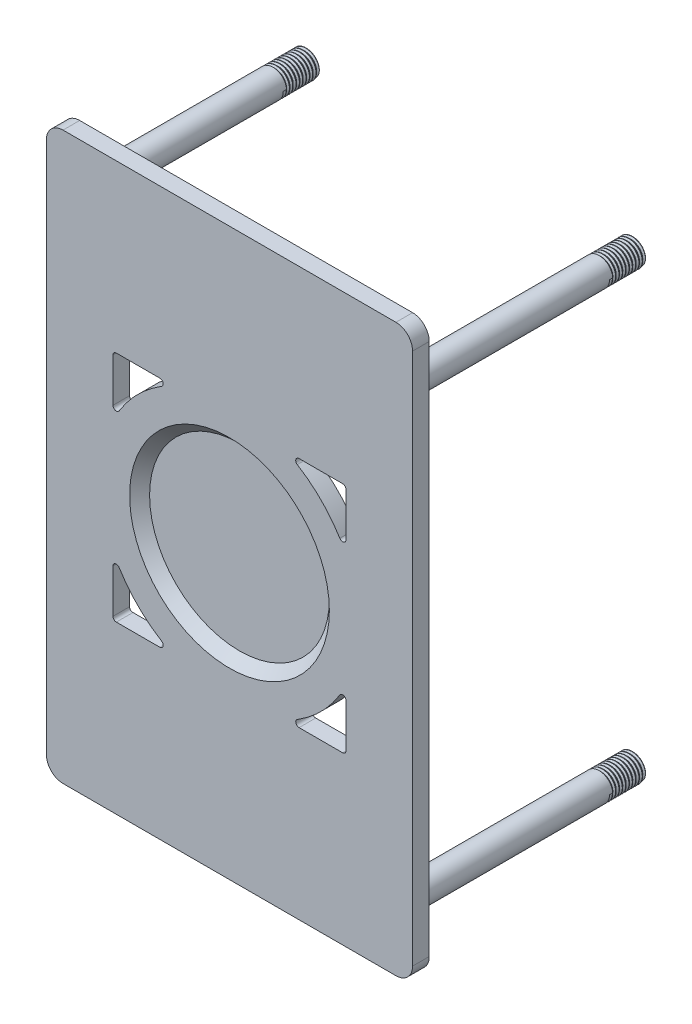
SolidWorks part; units mm, degrees
ref_plane "Ebene vorne" through (0, 0, 0) normal (0, 0, 1) x (1, 0, 0)
ref_plane "Ebene oben" through (0, 0, 0) normal (0, 1, 0) x (1, 0, 0)
ref_plane "Ebene rechts" through (0, 0, 0) normal (1, 0, 0) x (0, 0, -1)
sketch "Skizze1" plane through (0, 0, 0) normal (0, 0, 1) x (1, 0, 0)
  line L1 (-55, -85) -> (55, -85)
  line L2 (-55, -85) -> (-55, 85)
  line L3 (-55, 85) -> (55, 85)
  line L4 (55, -85) -> (55, 85)
  line L5 (-55, -85) -> (55, 85) construction
  line L6 (-55, 85) -> (55, -85) construction
  point P0 (0, 0)
  dimension "D1" = 110
  dimension "D2" = 170
extrude "Aufsatz-Linear austragen1" add sketch "Skizze1" along normal blind 5
sketch "Skizze2" plane through (0, 0, 5) normal (0, 0, 1) x (1, 0, 0)
  line L0 (-55, -85) -> (55, -85) construction
  line L1 (0, 85) -> (0, -85) construction
  line L2 (55, 85) -> (-55, 85) construction
  circle A1 centre (0, 0) radius 27
  dimension "D2" = 54
fillet "Verrundung1" radius 5 4 edges at (-55, -85, 2.5) (55, -85, 2.5) (55, 85, 2.5) (-55, 85, 2.5)
sketch "Skizze3" plane through (0, 0, 5) normal (0, 0, 1) x (1, 0, 0)
  line L0 (-35, 35) -> (-35, 17)
  line L1 (-35, -35) -> (35, -35) construction
  line L2 (-35, -35) -> (-35, 35) construction
  line L3 (-35, 35) -> (35, 35) construction
  line L4 (35, -35) -> (35, 35) construction
  line L5 (-35, -35) -> (35, 35) construction
  line L6 (-35, 35) -> (35, -35) construction
  line L7 (-35, 35) -> (-17, 35)
  line L8 (35, 35) -> (17, 35)
  line L9 (35, 35) -> (35, 17)
  line L10 (35, -35) -> (35, -17)
  line L11 (35, -35) -> (17, -35)
  line L12 (-35, -35) -> (-17, -35)
  line L13 (-35, -35) -> (-35, -17)
  arc A0 (-17, 35) -> (-35, 17) centre (0, 0) ccw
  arc A1 (35, 17) -> (17, 35) centre (0, 0) ccw
  arc A2 (17, -35) -> (35, -17) centre (0, 0) ccw
  arc A3 (-35, -17) -> (-17, -35) centre (0, 0) ccw
  point P0 (0, 0)
  point P21 (0, 0)
  dimension "D2" = 18
  dimension "D1" = 70
  dimension "D3" = 4
extrude "Schnitt-Linear austragen1" cut sketch "Skizze3" against normal through all
extrude "Schnitt-Linear austragen2" cut sketch "Skizze2" against normal blind 3
chamfer "Fase1" distance 3 angle 45 1 edges at (27, 0, 5)
sketch "Skizze4" plane through (0, 0, 0) normal (0, 0, -1) x (-1, 0, 0)
  line L0 (-50, 85) -> (50, 85) construction
  line L1 (-55, -80) -> (-55, 80) construction
  circle A0 centre (-49, 67) radius 4
  dimension "D1" = 18
  dimension "D3" = 8
  dimension "D2" = 6
extrude "Aufsatz-Linear austragen2" add sketch "Skizze4" along normal blind 69
chamfer "Fase2" distance 1 angle 45 1 edges at (45, 67, 0)
ref_plane "Ebene1" through (0, 0, -67) normal (0, 0, -1) x (-1, 0, 0)
sketch "Skizze5" plane through (0, 0, -67) normal (0, 0, -1) x (-1, 0, 0)
  circle A0 centre (-49, 67) radius 3
  circle A1 centre (-49, 67) radius 3.5
  dimension "D1" = 6
  dimension "D2" = 7
extrude "Schnitt-Linear austragen3" [suppressed] cut sketch "Skizze5" against normal blind 1
pattern_linear "Lineares Muster1" count 2 spacing 134 along (0, -1, 0) count 2 spacing 98 along (-1, 0, 0) of "Aufsatz-Linear austragen2", "Fase2"
fillet "Verrundung2" radius 1 12 edges at (-17, 35, 2.5) (-35, 35, 2.5) (-35, 17, 2.5) (-17, -35, 2.5) (-35, -17, 2.5) (-35, -35, 2.5) (35, -35, 2.5) (17, -35, 2.5) (35, -17, 2.5) (35, 17, 2.5) (35, 35, 2.5) (17, 35, 2.5)
thread "Gewinde1" pitch 1 method cut profile "Gewindeprofil1" start angle 0, offset 0, length 12, pitch 1, diameter 8
ref_plane "Ebene2" through (53, 67, -69) normal (0, -1, 0) x (1, 0, 0)
sketch "Gewindeprofil1" plane through (53, 67, -69) normal (0, -1, 0) x (1, 0, 0)
  line L0 (0, 0) -> (0, 1) construction
  line L11 (0, 0) -> (0, 0.875)
  line L12 (0, 0.875) -> (-0.5413, 0.5625)
  line L13 (-0.5413, 0.5625) -> (-0.5413, 0.3125)
  line L15 (-0.5413, 0.3125) -> (0, 0)
  line L17 (-0.5413, 0.4375) -> (0, 0.4375) construction
  point P2 (0, 0)
  dimension "Pitch" = 1
  dimension "Profile_Angle" = 60
  dimension "Profile_Land" = 0.25
  dimension "Profile_Height" = 0.5413
thread "Gewinde2" pitch 1 method cut profile "Gewindeprofil2" start angle 0, offset 0, length 12, pitch 1, diameter 8
ref_plane "Ebene3" through (53, -67, -69) normal (0, -1, 0) x (1, 0, 0)
sketch "Gewindeprofil2" plane through (53, -67, -69) normal (0, -1, 0) x (1, 0, 0)
  line L0 (0, 0) -> (0, 1) construction
  line L11 (0, 0) -> (0, 0.875)
  line L12 (0, 0.875) -> (-0.5413, 0.5625)
  line L13 (-0.5413, 0.5625) -> (-0.5413, 0.3125)
  line L15 (-0.5413, 0.3125) -> (0, 0)
  line L17 (-0.5413, 0.4375) -> (0, 0.4375) construction
  point P2 (0, 0)
  dimension "Pitch" = 1
  dimension "Profile_Angle" = 60
  dimension "Profile_Land" = 0.25
  dimension "Profile_Height" = 0.5413
thread "Gewinde3" pitch 1 method cut profile "Gewindeprofil3" start angle 0, offset 0, length 12, pitch 1, diameter 8
ref_plane "Ebene4" through (-45, -67, -69) normal (0, -1, 0) x (1, 0, 0)
sketch "Gewindeprofil3" plane through (-45, -67, -69) normal (0, -1, 0) x (1, 0, 0)
  line L0 (0, 0) -> (0, 1) construction
  line L11 (0, 0) -> (0, 0.875)
  line L12 (0, 0.875) -> (-0.5413, 0.5625)
  line L13 (-0.5413, 0.5625) -> (-0.5413, 0.3125)
  line L15 (-0.5413, 0.3125) -> (0, 0)
  line L17 (-0.5413, 0.4375) -> (0, 0.4375) construction
  point P2 (0, 0)
  dimension "Pitch" = 1
  dimension "Profile_Angle" = 60
  dimension "Profile_Land" = 0.25
  dimension "Profile_Height" = 0.5413
thread "Gewinde4" pitch 1 method cut profile "Gewindeprofil4" start angle 0, offset 0, length 12, pitch 1, diameter 8
ref_plane "Ebene5" through (-45, 67, -69) normal (0, -1, 0) x (1, 0, 0)
sketch "Gewindeprofil4" plane through (-45, 67, -69) normal (0, -1, 0) x (1, 0, 0)
  line L0 (0, 0) -> (0, 1) construction
  line L11 (0, 0) -> (0, 0.875)
  line L12 (0, 0.875) -> (-0.5413, 0.5625)
  line L13 (-0.5413, 0.5625) -> (-0.5413, 0.3125)
  line L15 (-0.5413, 0.3125) -> (0, 0)
  line L17 (-0.5413, 0.4375) -> (0, 0.4375) construction
  point P2 (0, 0)
  dimension "Pitch" = 1
  dimension "Profile_Angle" = 60
  dimension "Profile_Land" = 0.25
  dimension "Profile_Height" = 0.5413
sketch "Skizze10" plane through (0, 0, -69) normal (0, 0, -1) x (-1, 0, 0)
  line L0 (-49, 72) -> (-49, 62) construction
  line L2 (-60, -75) -> (60, -75)
  line L3 (-60, -75) -> (-60, 75)
  line L4 (-60, 75) -> (60, 75)
  line L5 (60, -75) -> (60, 75)
  line L6 (-60, -75) -> (60, 75) construction
  line L7 (-60, 75) -> (60, -75) construction
  circle A0 centre (-49, 67) radius 5 construction
  point P5 (0, 0)
  dimension "D1" = 150
  dimension "D2" = 120
extrude "Schnitt-Linear austragen4" cut sketch "Skizze10" against normal blind 2
